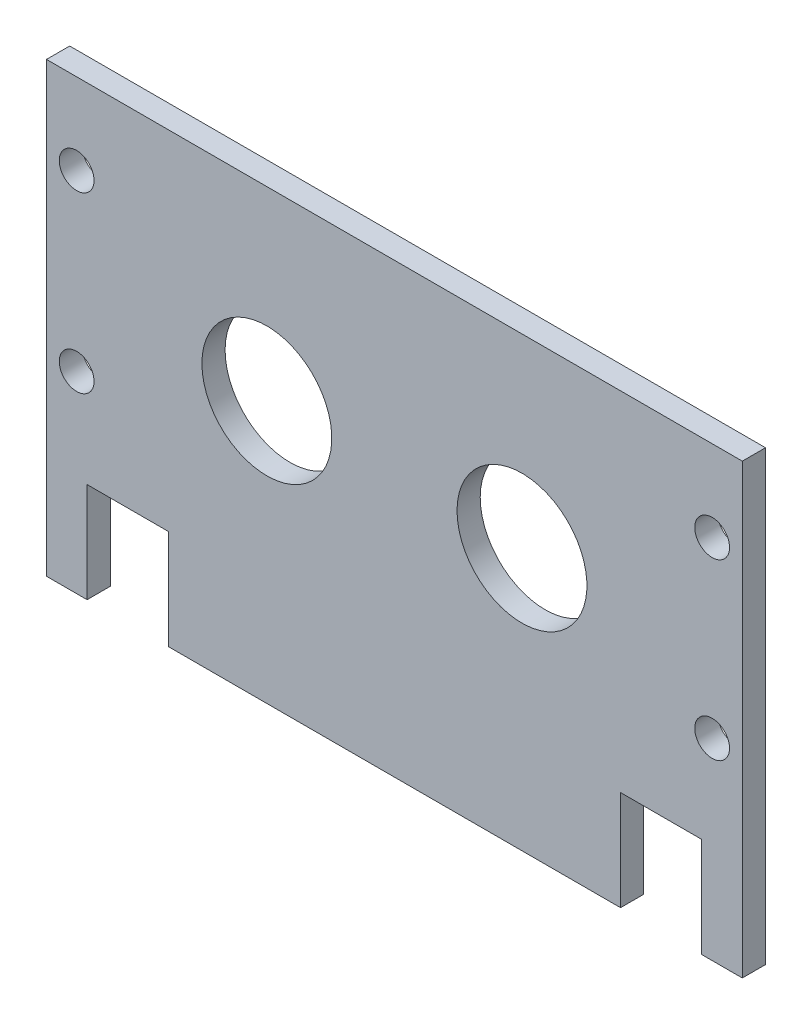
SolidWorks part; units mm, degrees
ref_plane "Front Plane" through (0, 0, 0) normal (0, 0, 1) x (1, 0, 0)
ref_plane "Top Plane" through (0, 0, 0) normal (0, 1, 0) x (1, 0, 0)
ref_plane "Right Plane" through (0, 0, 0) normal (1, 0, 0) x (0, 0, -1)
sketch "Çizim1" plane through (0, 0, 0) normal (0, 0, 1) x (1, 0, 0)
  line L1 (-150, 75) -> (150, 75)
  line L2 (-150, 75) -> (-150, -75)
  line L3 (-150, -75) -> (150, -75)
  line L4 (150, 75) -> (150, -75)
  line L5 (-150, 75) -> (150, -75) construction
  line L6 (-150, -75) -> (150, 75) construction
  point P0 (0, 0)
  dimension "D1" = 150
  dimension "D2" = 300
base flange "Taban-Flanş1" sketch "Çizim1" thickness 10 reverse thickness direction no parameters "D1"=0.7366
sketch "Çizim6" plane through (0, 0, -10) normal (0, 0, -1) x (-1, 0, 0)
  line L0 (55, -5) -> (-55, -5) construction
  line L1 (150, -75) -> (-150, -75) construction
  circle A0 centre (-55, -5) radius 28
  circle A1 centre (55, -5) radius 28
  point P2 (0, -5)
  dimension "D1" = 56
  dimension "D2" = 110
  dimension "D3" = 70
extrude "Kes-Ekstrüzyon1" cut sketch "Çizim6" against normal blind 10 normal cut yes
sketch "Çizim7" plane through (0, 0, -10) normal (0, 0, -1) x (-1, 0, 0)
  line L0 (-150, -75) -> (-150, 75) construction
  line L1 (-150, 75) -> (150, 75) construction
  line L2 (150, -75) -> (-150, -75) construction
  circle A0 centre (-137, 40) radius 7.5
  circle A1 centre (-137, -35) radius 7.5
  dimension "D2" = 15
  dimension "D1" = 13
  dimension "D3" = 35
  dimension "D4" = 40
extrude "Kes-Ekstrüzyon2" cut sketch "Çizim7" against normal blind 15 normal cut yes
mirror "Aynalama1" about plane through (0, 0, 0) normal (1, 0, 0) of "Kes-Ekstrüzyon2"
sketch "Çizim8" plane through (0, 0, -10) normal (0, 0, -1) x (-1, 0, 0)
  line L1 (-150, -75) -> (-132.5, -75)
  line L2 (-150, -75) -> (-150, -118)
  line L3 (-150, -118) -> (-132.5, -118)
  line L4 (-132.5, -75) -> (-132.5, -118)
  line L6 (-97.5, -75) -> (97.5, -75)
  line L7 (-97.5, -75) -> (-97.5, -118)
  line L8 (-97.5, -118) -> (97.5, -118)
  line L9 (97.5, -75) -> (97.5, -118)
  line L13 (132.5, -75) -> (150, -75)
  line L14 (132.5, -75) -> (132.5, -118)
  line L15 (132.5, -118) -> (150, -118)
  line L16 (150, -75) -> (150, -118)
  dimension "D1" = 43
  dimension "D2" = 300
  dimension "D3" = 17.5
  dimension "D4" = 35
  dimension "D5" = 195
  dimension "D6" = 35
  dimension "D7" = 75
  dimension "D8" = 75
  dimension "D9" = 75
  dimension "D10" = 132.5
base flange "Sekme1" sketch "Çizim8" thickness 10 reverse thickness direction no parameters "D1"=0.7366
sketch "Büküm-Çizgileri1" [suppressed] plane through (0, 0, 0) normal (0, 1, 0) x (1, 0, 0)
sketch "Sınırlandırma-Kutusu1" [suppressed] plane through (0, 0, 0) normal (0, 1, 0) x (1, 0, 0)
sheet metal parameters "Sac-Levha1" thickness 10 parameters "D1"=0.7366
flat pattern "Düz-Çoğaltma1" [suppressed]
sketch "Büküm-Çizgileri2" plane through (0, 0, 0) normal (0, 1, 0) x (1, 0, 0)
sketch3d "Sınırlandırma-Kutusu2" [suppressed]
  line L0 (165, -75, 0) -> (-165, -75, 0) construction
  line L1 (165, 75, 0) -> (-165, 75, 0) construction
  line L2 (165, -75, 0) -> (165, 75, 0) construction
  line L3 (-165, -75, 0) -> (-165, 75, 0) construction
sheet metal parameters "Sac-Levha2" thickness 10 parameters "D1"=0.7366
flat pattern "Düz-Çoğaltma1"
sketch "Büküm-Çizgileri2" plane through (0, 0, 0) normal (0, 1, 0) x (1, 0, 0)
sketch3d "Sınırlandırma-Kutusu2" [suppressed]
  line L0 (-150, -75, 0) -> (150, -75, 0) construction
  line L1 (-150, 75, 0) -> (150, 75, 0) construction
  line L2 (-150, -75, 0) -> (-150, 75, 0) construction
  line L3 (150, -75, 0) -> (150, 75, 0) construction
sheet metal parameters "Sac-Levha3" thickness 10 parameters "D1"=0.7366
flat pattern "Düz-Çoğaltma1"
sketch "Büküm-Çizgileri2" plane through (0, 0, 0) normal (0, 1, 0) x (1, 0, 0)
sketch3d "Sınırlandırma-Kutusu2" [suppressed]
  line L0 (-150, -75, 0) -> (150, -75, 0) construction
  line L1 (-150, 75, 0) -> (150, 75, 0) construction
  line L2 (-150, -75, 0) -> (-150, 75, 0) construction
  line L3 (150, -75, 0) -> (150, 75, 0) construction
sheet metal parameters "Sac-Levha4" thickness 10 parameters "D1"=0.7366
flat pattern "Düz-Çoğaltma1"
sketch "Büküm-Çizgileri2" plane through (0, 0, 0) normal (0, 1, 0) x (1, 0, 0)
sketch3d "Sınırlandırma-Kutusu2" [suppressed]
  line L0 (-150, -75, 0) -> (150, -75, 0) construction
  line L1 (-150, 75, 0) -> (150, 75, 0) construction
  line L2 (-150, -75, 0) -> (-150, 75, 0) construction
  line L3 (150, -75, 0) -> (150, 75, 0) construction
sheet metal parameters "Sac-Levha5" thickness 10 parameters "D1"=0.7366
flat pattern "Düz-Çoğaltma5"
sketch "Büküm-Çizgileri3" plane through (0, 0, 0) normal (0, 1, 0) x (1, 0, 0)
sketch3d "Sınırlandırma-Kutusu3" [suppressed]
  line L0 (-150, -118, 0) -> (150, -118, 0) construction
  line L1 (-150, 75, 0) -> (150, 75, 0) construction
  line L2 (-150, -118, 0) -> (-150, 75, 0) construction
  line L3 (150, -118, 0) -> (150, 75, 0) construction
